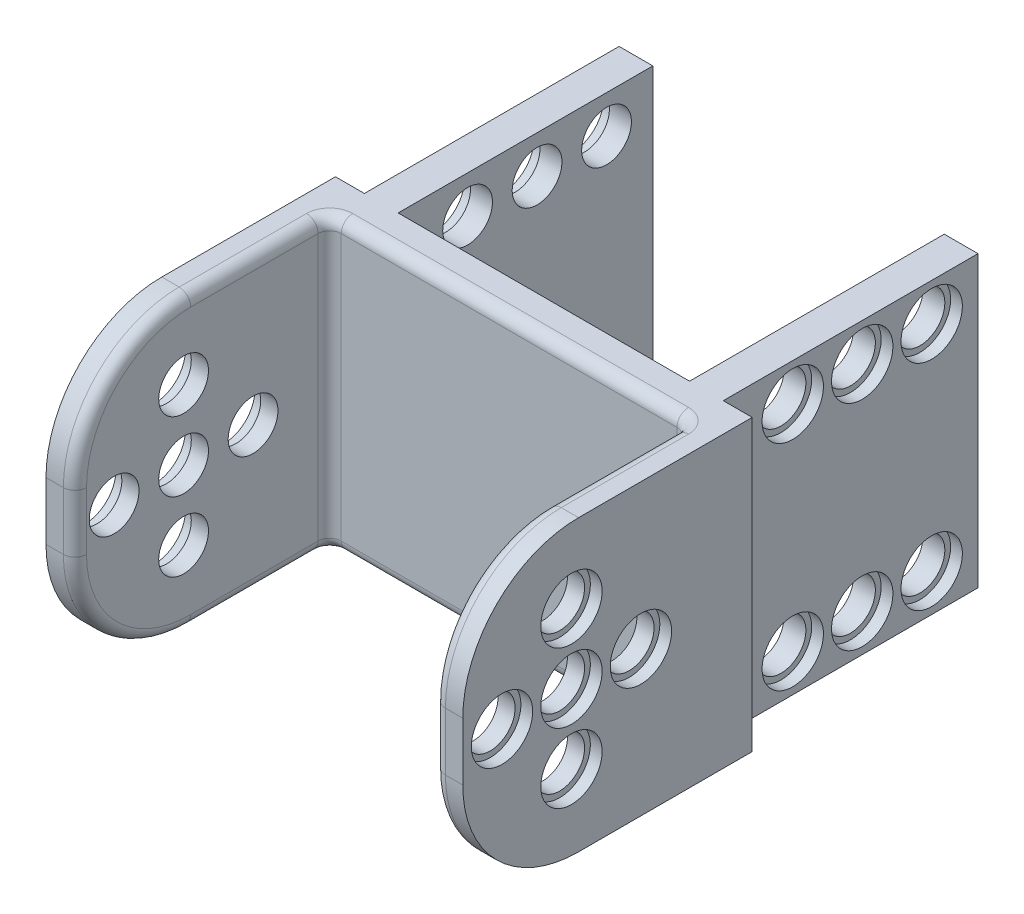
SolidWorks part; units mm, degrees
ref_plane "Alzado" through (0, 0, 0) normal (0, 0, 1) x (1, 0, 0)
ref_plane "Planta" through (0, 0, 0) normal (0, 1, 0) x (1, 0, 0)
ref_plane "Vista lateral" through (0, 0, 0) normal (1, 0, 0) x (0, 0, -1)
sketch "Croquis1" plane through (0, 0, 0) normal (0, 0, 1) x (1, 0, 0)
  line L1 (0, 0) -> (36, 0)
  line L2 (0, 0) -> (0, 25)
  line L3 (0, 25) -> (36, 25)
  line L4 (36, 0) -> (36, 25)
  dimension "D1" = 36
  dimension "D2" = 25
extrude "Saliente-Extruir1" add sketch "Croquis1" along normal blind 25
sketch "Croquis2" plane through (0, 0, 25) normal (0, 0, 1) x (1, 0, 0)
  line L0 (18, 25) -> (18, 0) construction
  line L1 (36, 25) -> (0, 25) construction
  line L2 (0, 0) -> (36, 0) construction
  line L3 (18, 12.5) -> (36, 12.5) construction
  line L4 (36, 0) -> (36, 25) construction
  line L6 (2.5, 25) -> (33.5, 25)
  line L7 (2.5, 25) -> (2.5, 0)
  line L8 (2.5, 0) -> (33.5, 0)
  line L9 (33.5, 25) -> (33.5, 0)
  line L10 (2.5, 25) -> (33.5, 0) construction
  line L11 (2.5, 0) -> (33.5, 25) construction
  dimension "D1" = 31
extrude "Cortar-Extruir1" cut sketch "Croquis2" against normal blind 22
sketch "Croquis3" plane through (36, 0, 0) normal (1, 0, 0) x (0, 0, -1)
  line L0 (0, 12.5) -> (-25, 12.5) construction
  line L1 (0, 0) -> (0, 25) construction
  line L2 (-25, 0) -> (-25, 25) construction
  line L3 (0, 12.5) -> (-7, 12.5) construction
  line L4 (-21.6154, 12.5) -> (-9.6154, 12.5) construction
  line L5 (-15.6154, 18.5) -> (-15.6154, 12.5) construction
  circle A0 centre (-15.6154, 18.5) radius 2.15
  circle A1 centre (-9.6154, 12.5) radius 2.15
  circle A2 centre (-21.6154, 12.5) radius 2.15
  circle A3 centre (-15.6154, 6.5) radius 2.15
  circle A4 centre (-15.6154, 18.5) radius 2.65
  circle A5 centre (-9.6154, 12.5) radius 2.65
  circle A6 centre (-21.6154, 12.5) radius 2.65
  circle A7 centre (-15.6154, 6.5) radius 2.65
  circle A8 centre (-15.6154, 12.5) radius 2.15
  circle A9 centre (-15.6154, 12.5) radius 2.65
  dimension "D2" = 5.3
  dimension "D3" = 5.3
  dimension "D4" = 4.3
  dimension "D5" = 4.3
  dimension "D1" = 7
extrude "Cortar-Extruir2" cut sketch "Croquis3" against normal through all contours A0 | A1 | A8 | A2 | A3 region at (36, 18.5, 15.6154) region at (36, 12.5, 9.6154) region at (36, 12.5, 21.6154) region at (36, 6.5, 15.6154) region at (36, 12.5, 15.6154)
extrude "Cortar-Extruir3" cut sketch "Croquis3<3>" against normal blind 1.015 contours A4 A0 | A5 A1 | A9 A8 | A6 A2 | A7 A3 region at (36, 18.5, 18.1904) region at (36, 12.5, 12.1904) region at (36, 12.5, 24.1904) region at (36, 6.5, 18.1904) region at (36, 12.5, 18.1904)
sketch "Croquis3<3>" plane through (36, 0, 0) normal (1, 0, 0) x (0, 0, -1) same geometry as "Croquis3"
sketch "Croquis4" plane through (0, 0, 0) normal (-1, 0, 0) x (0, 0, 1)
  circle A0 centre (15.6154, 18.5) radius 2.65
  circle A1 centre (21.6154, 12.5) radius 2.65
  circle A2 centre (15.6154, 6.5) radius 2.65
  circle A3 centre (15.6154, 12.5) radius 2.65
  circle A4 centre (9.6154, 12.5) radius 2.65
  circle M1 centre (15.6154, 6.5) radius 2.15
  circle M2 centre (21.6154, 12.5) radius 2.15
  circle M3 centre (15.6154, 12.5) radius 2.15
  circle M4 centre (9.6154, 12.5) radius 2.15
  circle M5 centre (15.6154, 18.5) radius 2.15
  dimension "D1" = 5.3
extrude "Cortar-Extruir4" cut sketch "Croquis4" against normal blind 1.015 contours A0 M5 | A1 M2 | A3 M3 | A4 M4 | A2 M1 region at (0, 18.5, 13.0403) region at (0, 12.5, 19.0403) region at (0, 6.5, 13.0403) region at (0, 12.5, 13.0403) region at (0, 12.5, 7.0403)
sketch "Croquis5" plane through (0, 0, 0) normal (0, 0, -1) x (-1, 0, 0)
  line L0 (-18, 25) -> (-18, 0) construction
  line L1 (-36, 25) -> (0, 25) construction
  line L2 (0, 0) -> (-36, 0) construction
  line L3 (-18, 12.5) -> (0, 12.5) construction
  line L4 (0, 25) -> (0, 0) construction
  line L6 (-33.5, 25) -> (-2.5, 25)
  line L7 (-33.5, 25) -> (-33.5, 0)
  line L8 (-33.5, 0) -> (-2.5, 0)
  line L9 (-2.5, 25) -> (-2.5, 0)
  line L10 (-33.5, 25) -> (-2.5, 0) construction
  line L11 (-33.5, 0) -> (-2.5, 25) construction
  dimension "D1" = 31
extrude "Saliente-Extruir2" add sketch "Croquis5" along normal blind 22
sketch "Croquis6" plane through (0, 0, -22) normal (0, 0, -1) x (-1, 0, 0)
  line L0 (-18, 25) -> (-18, 0) construction
  line L1 (-2.5, 25) -> (-33.5, 25) construction
  line L2 (-33.5, 0) -> (-2.5, 0) construction
  line L3 (-18, 12.5) -> (-2.5, 12.5) construction
  line L4 (-2.5, 0) -> (-2.5, 25) construction
  line L6 (-30.585, 25) -> (-5.415, 25)
  line L7 (-30.585, 25) -> (-30.585, 0)
  line L8 (-30.585, 0) -> (-5.415, 0)
  line L9 (-5.415, 25) -> (-5.415, 0)
  line L10 (-30.585, 25) -> (-5.415, 0) construction
  line L11 (-30.585, 0) -> (-5.415, 25) construction
  dimension "D1" = 25.17
extrude "Cortar-Extruir5" cut sketch "Croquis6" against normal blind 22
sketch "Croquis7" plane through (2.5, 0, 0) normal (-1, 0, 0) x (0, 0, 1)
  line L0 (-11, 25) -> (-11, 0) construction
  line L1 (-22, 25) -> (0, 25) construction
  line L2 (-22, 0) -> (0, 0) construction
  line L3 (-22, 12.5) -> (-11, 12.5) construction
  line L4 (-22, 0) -> (-22, 25) construction
  line L5 (-11, 12.5) -> (0, 12.5) construction
  line L6 (0, 0) -> (0, 25) construction
sketch "Croquis8" plane through (2.5, 0, 0) normal (-1, 0, 0) x (0, 0, 1)
  circle A0 centre (-18, 21.75) radius 2.15
  circle A1 centre (-12, 21.75) radius 2.15
  circle A2 centre (-6, 21.75) radius 2.15
  circle A3 centre (-6, 21.75) radius 2.65
  circle A4 centre (-18, 21.75) radius 2.65
  circle A5 centre (-18, 3.25) radius 2.15
  circle A6 centre (-12, 3.25) radius 2.15
  circle A7 centre (-6, 3.25) radius 2.15
  circle A8 centre (-6, 3.25) radius 2.65
  circle A9 centre (-18, 3.25) radius 2.65
  circle A10 centre (-12, 21.75) radius 2.65
  circle A11 centre (-12, 3.25) radius 2.65
extrude "Cortar-Extruir6" cut sketch "Croquis8" against normal through all contours A0 | A1 | A2 | A5 | A6 | A7 region at (2.5, 21.75, -18) region at (2.5, 21.75, -12) region at (2.5, 21.75, -6) region at (2.5, 3.25, -18) region at (2.5, 3.25, -12) region at (2.5, 3.25, -6)
extrude "Cortar-Extruir7" cut sketch "Croquis8<3>" against normal blind 1.015 contours A4 A0 | A3 A2 | A9 A5 | A8 A7 | A10 A1 | A11 A6 region at (2.5, 21.75, -8.575) region at (2.5, 21.75, -20.575) region at (2.5, 3.25, -8.575) region at (2.5, 3.25, -20.575) region at (2.5, 21.75, -14.575) region at (2.5, 3.25, -14.575)
sketch "Croquis8<3>" plane through (2.5, 0, 0) normal (-1, 0, 0) x (0, 0, 1) same geometry as "Croquis8"
sketch "Croquis10" plane through (33.5, 0, 0) normal (1, 0, 0) x (0, 0, -1)
  circle A0 centre (6, 21.75) radius 2.65
  circle A1 centre (18, 21.75) radius 2.65
  circle A2 centre (6, 3.25) radius 2.65
  circle A3 centre (18, 3.25) radius 2.65
  circle A4 centre (12, 3.25) radius 2.65
  circle A5 centre (12, 21.75) radius 2.65
  circle M1 centre (6, 3.25) radius 2.15
  circle M2 centre (12, 3.25) radius 2.15
  circle M3 centre (18, 3.25) radius 2.15
  circle M4 centre (6, 21.75) radius 2.15
  circle M5 centre (12, 21.75) radius 2.15
  circle M6 centre (18, 21.75) radius 2.15
extrude "Cortar-Extruir8" cut sketch "Croquis10" against normal blind 1.015 contours A0 M4 | A5 M5 | A1 M6 | A2 M1 | A4 M2 | A3 M3 region at (33.5, 21.75, -3.425) region at (33.5, 21.75, -15.425) region at (33.5, 3.25, -3.425) region at (33.5, 3.25, -15.425) region at (33.5, 3.25, -9.425) region at (33.5, 21.75, -9.425)
fillet "Redondeo2" radius 10 4 edges at (1.25, 0, 25) (34.75, 0, 25) (34.75, 25, 25) (1.25, 25, 25)
fillet "Redondeo3" radius 1 1 edges at (33.5, 12.5, 3)
fillet "Redondeo4" radius 1 1 edges at (2.5, 12.5, 3)
fillet "Redondeo5" radius 1 16 edges at (2.7929, 0, 3.2929) (2.5, 0, 9.5) (2.5, 2.9289, 22.0711) (2.5, 12.5, 25) (2.5, 22.0711, 22.0711) (2.5, 25, 9.5) (2.7929, 25, 3.2929) (33.2071, 25, 3.2929) (33.5, 25, 9.5) (33.5, 22.0711, 22.0711) (33.5, 12.5, 25) (33.5, 2.9289, 22.0711) (33.5, 0, 9.5) (33.2071, 0, 3.2929) (18, 25, 3) (18, 0, 3)
